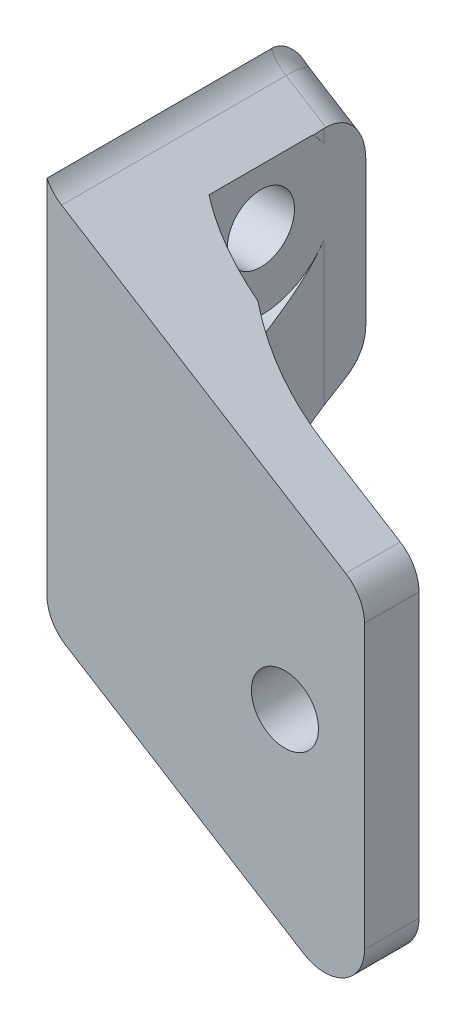
SolidWorks part; units mm, degrees
ref_plane "Front Plane" through (0, 0, 0) normal (0, 0, 1) x (1, 0, 0)
ref_plane "Top Plane" through (0, 0, 0) normal (0, 1, 0) x (1, 0, 0)
ref_plane "Right Plane" through (0, 0, 0) normal (1, 0, 0) x (0, 0, -1)
sketch "Sketch1" plane through (0, 0, 0) normal (0, 0, 1) x (1, 0, 0)
  line L12 (466.0404, -267.15) -> (19.05, 11.077) construction
  line L28 (55.1575, -11.3979) -> (21.2899, 9.6828)
  line L32 (5.7912, 19.05) -> (-5.7912, 19.05)
  line L33 (-19.05, -19.05) -> (-19.05, -52.4)
  line L34 (-14.3, -57.15) -> (52.6474, -57.15)
  line L35 (57.3974, -52.4) -> (57.3974, -15.4305)
  line L36 (-19.05, -13.7235) -> (-19.05, -19.05)
  line L37 (-19.05, -19.05) -> (-19.0952, -18.9748)
  line L38 (-19.05, 5.7912) -> (-19.05, -5.7912)
  line L44 (-19.05, -5.7912) -> (-19.05, -6.9643)
  line L45 (-19.05, -8.9963) -> (-19.05, -13.7235)
  line L46 (-13.7235, -19.05) -> (-8.9963, -19.05)
  line L47 (-6.9643, -19.05) -> (-5.7912, -19.05)
  line L48 (-4.064, -17.3228) -> (-4.064, -16.7132)
  line L49 (-5.7912, -14.986) -> (-8.9963, -14.986)
  line L50 (-9.909, -12.7826) -> (-5.0152, -7.8889)
  line L51 (-2.833, -6.985) -> (2.833, -6.985)
  line L52 (5.0152, -7.8889) -> (9.909, -12.7826)
  line L53 (8.9963, -14.986) -> (5.7912, -14.986)
  line L54 (4.064, -16.7132) -> (4.064, -17.3228)
  line L55 (5.7912, -19.05) -> (6.9643, -19.05)
  line L56 (8.9963, -19.05) -> (13.7235, -19.05)
  line L57 (19.05, -13.7235) -> (19.05, -8.9963)
  line L58 (19.05, -6.9643) -> (19.05, -5.7912)
  line L59 (17.3228, -4.064) -> (16.7132, -4.064)
  line L60 (14.986, -5.7912) -> (14.986, -8.9963)
  line L61 (12.7826, -9.909) -> (7.8889, -5.0152)
  line L62 (6.985, -2.833) -> (6.985, 2.833)
  line L63 (7.8889, 5.0152) -> (12.7826, 9.909)
  line L64 (14.986, 8.9963) -> (14.986, 5.7912)
  line L65 (16.7132, 4.064) -> (17.3228, 4.064)
  line L66 (19.05, 5.7912) -> (19.05, 6.9643)
  line L67 (19.05, 8.9963) -> (19.05, 13.7235)
  line L68 (13.7235, 19.05) -> (8.9963, 19.05)
  line L69 (6.9643, 19.05) -> (5.7912, 19.05)
  line L70 (4.064, 17.3228) -> (4.064, 16.7132)
  line L71 (5.7912, 14.986) -> (8.9963, 14.986)
  line L72 (9.909, 12.7826) -> (5.0152, 7.8889)
  line L73 (2.833, 6.985) -> (-2.833, 6.985)
  line L74 (-5.0152, 7.8889) -> (-9.909, 12.7826)
  line L75 (-8.9963, 14.986) -> (-5.7912, 14.986)
  line L76 (-4.064, 16.7132) -> (-4.064, 17.3228)
  line L77 (-5.7912, 19.05) -> (-6.9643, 19.05)
  line L78 (-8.9963, 19.05) -> (-13.7235, 19.05)
  line L79 (-19.05, 13.7235) -> (-19.05, 8.9963)
  line L80 (-19.05, 6.9643) -> (-19.05, 5.7912)
  line L81 (-17.3228, 4.064) -> (-16.7132, 4.064)
  line L82 (-14.986, 5.7912) -> (-14.986, 8.9963)
  line L83 (-12.7826, 9.909) -> (-7.8889, 5.0152)
  line L84 (-6.985, 2.833) -> (-6.985, -2.833)
  line L85 (-7.8889, -5.0152) -> (-12.7826, -9.909)
  line L86 (-14.986, -8.9963) -> (-14.986, -5.7912)
  line L87 (-16.7132, -4.064) -> (-17.3228, -4.064)
  line L88 (-19.05, -5.7912) -> (-19.05, -6.9643)
  line L89 (-19.05, -8.9963) -> (-19.05, -13.7235)
  line L111 (19.05, 13.7154) -> (19.05, 13.7235)
  line L112 (13.7235, 19.05) -> (8.9963, 19.05)
  line L113 (6.9643, 19.05) -> (5.7912, 19.05)
  line L121 (-5.7912, 19.05) -> (-6.9643, 19.05)
  line L122 (-8.9963, 19.05) -> (-13.7235, 19.05)
  line L123 (-19.05, 13.7235) -> (-19.05, 8.9963)
  line L124 (-19.05, 6.9643) -> (-19.05, 5.7912)
  circle A2 centre (0, 0) radius 4.5
  circle A3 centre (0, -38.1) radius 3.25
  circle A5 centre (47.9138, -29.0681) radius 4
  arc A6 (-19.05, -52.4) -> (-14.3, -57.15) centre (-14.3, -52.4) ccw
  arc A7 (52.6474, -57.15) -> (57.3974, -52.4) centre (52.6474, -52.4) ccw
  arc A8 (57.3974, -15.4305) -> (55.1575, -11.3979) centre (52.6474, -15.4305) ccw
  arc A9 (21.2899, 9.6828) -> (19.05, 13.7154) centre (23.8, 13.7154) cw
  arc A52 (-19.05, -8.9963) -> (-19.05, -6.9643) centre (-19.05, -7.9803) ccw
  arc A53 (-18.8293, -15.7312) -> (-19.05, -13.7235) centre (-19.05, -14.7395) ccw
  arc A54 (-18.8293, -15.7312) -> (-15.7312, -18.8293) centre (-14.3002, -14.3002) ccw
  arc A55 (-13.7235, -19.05) -> (-15.7312, -18.8293) centre (-14.7395, -19.05) ccw
  arc A56 (-6.9643, -19.05) -> (-8.9963, -19.05) centre (-7.9803, -19.05) ccw
  arc A57 (-5.7912, -19.05) -> (-4.064, -17.3228) centre (-5.7912, -17.3228) ccw
  arc A58 (-4.064, -16.7132) -> (-5.7912, -14.986) centre (-5.7912, -16.7132) ccw
  arc A59 (-9.909, -12.7826) -> (-8.9963, -14.986) centre (-8.9963, -13.6953) ccw
  arc A60 (-2.833, -6.985) -> (-5.0152, -7.8889) centre (-2.833, -10.0711) ccw
  arc A61 (5.0152, -7.8889) -> (2.833, -6.985) centre (2.833, -10.0711) ccw
  arc A62 (8.9963, -14.986) -> (9.909, -12.7826) centre (8.9963, -13.6953) ccw
  arc A63 (5.7912, -14.986) -> (4.064, -16.7132) centre (5.7912, -16.7132) ccw
  arc A64 (4.064, -17.3228) -> (5.7912, -19.05) centre (5.7912, -17.3228) ccw
  arc A65 (8.9963, -19.05) -> (6.9643, -19.05) centre (7.9803, -19.05) ccw
  arc A66 (15.7312, -18.8293) -> (13.7235, -19.05) centre (14.7395, -19.05) ccw
  arc A67 (15.7312, -18.8293) -> (18.8293, -15.7312) centre (14.3002, -14.3002) ccw
  arc A68 (19.05, -13.7235) -> (18.8293, -15.7312) centre (19.05, -14.7395) ccw
  arc A69 (19.05, -6.9643) -> (19.05, -8.9963) centre (19.05, -7.9803) ccw
  arc A70 (19.05, -5.7912) -> (17.3228, -4.064) centre (17.3228, -5.7912) ccw
  arc A71 (16.7132, -4.064) -> (14.986, -5.7912) centre (16.7132, -5.7912) ccw
  arc A72 (12.7826, -9.909) -> (14.986, -8.9963) centre (13.6953, -8.9963) ccw
  arc A73 (6.985, -2.833) -> (7.8889, -5.0152) centre (10.0711, -2.833) ccw
  arc A74 (7.8889, 5.0152) -> (6.985, 2.833) centre (10.0711, 2.833) ccw
  arc A75 (14.986, 8.9963) -> (12.7826, 9.909) centre (13.6953, 8.9963) ccw
  arc A76 (14.986, 5.7912) -> (16.7132, 4.064) centre (16.7132, 5.7912) ccw
  arc A77 (17.3228, 4.064) -> (19.05, 5.7912) centre (17.3228, 5.7912) ccw
  arc A78 (19.05, 8.9963) -> (19.05, 6.9643) centre (19.05, 7.9803) ccw
  arc A79 (18.8293, 15.7312) -> (19.05, 13.7235) centre (19.05, 14.7395) ccw
  arc A80 (18.8293, 15.7312) -> (15.7312, 18.8293) centre (14.3002, 14.3002) ccw
  arc A81 (13.7235, 19.05) -> (15.7312, 18.8293) centre (14.7395, 19.05) ccw
  arc A82 (6.9643, 19.05) -> (8.9963, 19.05) centre (7.9803, 19.05) ccw
  arc A83 (5.7912, 19.05) -> (4.064, 17.3228) centre (5.7912, 17.3228) ccw
  arc A84 (4.064, 16.7132) -> (5.7912, 14.986) centre (5.7912, 16.7132) ccw
  arc A85 (9.909, 12.7826) -> (8.9963, 14.986) centre (8.9963, 13.6953) ccw
  arc A86 (2.833, 6.985) -> (5.0152, 7.8889) centre (2.833, 10.0711) ccw
  arc A87 (-5.0152, 7.8889) -> (-2.833, 6.985) centre (-2.833, 10.0711) ccw
  arc A88 (-8.9963, 14.986) -> (-9.909, 12.7826) centre (-8.9963, 13.6953) ccw
  arc A89 (-5.7912, 14.986) -> (-4.064, 16.7132) centre (-5.7912, 16.7132) ccw
  arc A90 (-4.064, 17.3228) -> (-5.7912, 19.05) centre (-5.7912, 17.3228) ccw
  arc A91 (-8.9963, 19.05) -> (-6.9643, 19.05) centre (-7.9803, 19.05) ccw
  arc A92 (-15.7312, 18.8293) -> (-13.7235, 19.05) centre (-14.7395, 19.05) ccw
  arc A93 (-15.7312, 18.8293) -> (-18.8293, 15.7312) centre (-14.3002, 14.3002) ccw
  arc A94 (-19.05, 13.7235) -> (-18.8293, 15.7312) centre (-19.05, 14.7395) ccw
  arc A95 (-19.05, 6.9643) -> (-19.05, 8.9963) centre (-19.05, 7.9803) ccw
  arc A96 (-19.05, 5.7912) -> (-17.3228, 4.064) centre (-17.3228, 5.7912) ccw
  arc A97 (-16.7132, 4.064) -> (-14.986, 5.7912) centre (-16.7132, 5.7912) ccw
  arc A98 (-12.7826, 9.909) -> (-14.986, 8.9963) centre (-13.6953, 8.9963) ccw
  arc A99 (-6.985, 2.833) -> (-7.8889, 5.0152) centre (-10.0711, 2.833) ccw
  arc A100 (-7.8889, -5.0152) -> (-6.985, -2.833) centre (-10.0711, -2.833) ccw
  arc A101 (-14.986, -8.9963) -> (-12.7826, -9.909) centre (-13.6953, -8.9963) ccw
  arc A102 (-14.986, -5.7912) -> (-16.7132, -4.064) centre (-16.7132, -5.7912) ccw
  arc A103 (-17.3228, -4.064) -> (-19.05, -5.7912) centre (-17.3228, -5.7912) ccw
  arc A104 (-19.05, -8.9963) -> (-19.05, -6.9643) centre (-19.05, -7.9803) ccw
  arc A105 (-18.8293, -15.7312) -> (-19.05, -13.7235) centre (-19.05, -14.7395) ccw
  arc A131 (18.8293, 15.7312) -> (19.05, 13.7235) centre (19.05, 14.7395) ccw
  arc A132 (18.8293, 15.7312) -> (15.7312, 18.8293) centre (14.3002, 14.3002) ccw
  arc A133 (13.7235, 19.05) -> (15.7312, 18.8293) centre (14.7395, 19.05) ccw
  arc A134 (6.9643, 19.05) -> (8.9963, 19.05) centre (7.9803, 19.05) ccw
  arc A143 (-8.9963, 19.05) -> (-6.9643, 19.05) centre (-7.9803, 19.05) ccw
  arc A144 (-15.7312, 18.8293) -> (-13.7235, 19.05) centre (-14.7395, 19.05) ccw
  arc A145 (-15.7312, 18.8293) -> (-18.8293, 15.7312) centre (-14.3002, 14.3002) ccw
  arc A146 (-19.05, 13.7235) -> (-18.8293, 15.7312) centre (-19.05, 14.7395) ccw
  arc A147 (-19.05, 6.9643) -> (-19.05, 8.9963) centre (-19.05, 7.9803) ccw
  dimension "D2" = 4.75
  dimension "D1" = 0
extrude "Boss-Extrude1" add sketch "Sketch1" along normal blind 6.5
sketch "Sketch2" plane through (0, 0, 0) normal (0, 0, -1) x (-1, 0, 0)
  line L53 (-19.55, -57.15) -> (14.3, -57.15)
  line L54 (19.05, -52.4) -> (19.05, -8.9963)
  line L55 (19.05, -6.9643) -> (19.05, 6.9643)
  line L56 (19.05, 8.9963) -> (19.05, 13.7235)
  line L57 (13.7235, 19.05) -> (8.9963, 19.05)
  line L58 (6.9643, 19.05) -> (-6.9643, 19.05)
  line L59 (-8.9963, 19.05) -> (-13.7235, 19.05)
  line L61 (-19.55, -14.612) -> (-19.55, 11.5941)
  line L63 (14.3, -57.15) -> (-52.6474, -57.15) construction
  line L64 (-35.024, -43.7437) -> (-1.1564, -22.663)
  line L65 (-35.024, -43.7437) -> (-19.55, -34.112)
  line L66 (14.3, -57.15) -> (-52.6474, -57.15)
  line L67 (-35.024, -43.7437) -> (-55.2813, -56.3528)
  line L134 (19.05, -8.9963) -> (19.05, -52.4)
  line L135 (14.3, -57.15) -> (-19.55, -57.15)
  line L136 (-19.55, -14.612) -> (-19.55, -34.112)
  arc A157 (14.3, -57.15) -> (19.05, -52.4) centre (14.3, -52.4) ccw
  arc A170 (14.3, -57.15) -> (19.05, -52.4) centre (14.3, -52.4) ccw
  arc A171 (19.05, -6.9643) -> (19.05, -8.9963) centre (19.05, -7.9803) ccw
  arc A172 (19.05, 8.9963) -> (19.05, 6.9643) centre (19.05, 7.9803) ccw
  arc A173 (18.8293, 15.7312) -> (19.05, 13.7235) centre (19.05, 14.7395) ccw
  arc A174 (18.8293, 15.7312) -> (15.7312, 18.8293) centre (14.3002, 14.3002) ccw
  arc A175 (13.7235, 19.05) -> (15.7312, 18.8293) centre (14.7395, 19.05) ccw
  arc A176 (6.9643, 19.05) -> (8.9963, 19.05) centre (7.9803, 19.05) ccw
  arc A177 (-8.9963, 19.05) -> (-6.9643, 19.05) centre (-7.9803, 19.05) ccw
  arc A178 (-15.7312, 18.8293) -> (-13.7235, 19.05) centre (-14.7395, 19.05) ccw
  arc A179 (-15.7312, 18.8293) -> (-18.8293, 15.7312) centre (-14.3002, 14.3002) ccw
  arc A180 (-19.05, 13.7235) -> (-18.8293, 15.7312) centre (-19.05, 14.7395) ccw
  arc A181 (-19.55, 11.5941) -> (-19.05, 13.7154) centre (-23.8, 13.7154) ccw
  arc A182 (-57.3974, -52.4) -> (-52.6474, -57.15) centre (-52.6474, -52.4) ccw construction
  arc A183 (-55.2813, -56.3528) -> (-52.6474, -57.15) centre (-52.6474, -52.4) ccw
  line M170 (19.05, -52.4) -> (19.05, -8.9963)
  arc M171 (19.05, -8.9963) -> (19.05, -6.9643) centre (19.05, -7.9803) cw
  line M172 (19.05, -6.9643) -> (19.05, 6.9643)
  arc M173 (19.05, 6.9643) -> (19.05, 8.9963) centre (19.05, 7.9803) cw
  line M174 (19.05, 8.9963) -> (19.05, 13.7235)
  arc M175 (19.05, 13.7235) -> (18.8293, 15.7312) centre (19.05, 14.7395) cw
  arc M176 (18.8293, 15.7312) -> (15.7312, 18.8293) centre (14.3002, 14.3002) ccw
  arc M177 (15.7312, 18.8293) -> (13.7235, 19.05) centre (14.7395, 19.05) cw
  line M178 (13.7235, 19.05) -> (8.9963, 19.05)
  arc M179 (8.9963, 19.05) -> (6.9643, 19.05) centre (7.9803, 19.05) cw
  line M180 (6.9643, 19.05) -> (-6.9643, 19.05)
  arc M181 (-6.9643, 19.05) -> (-8.9963, 19.05) centre (-7.9803, 19.05) cw
  line M182 (-8.9963, 19.05) -> (-13.7235, 19.05)
  arc M183 (-13.7235, 19.05) -> (-15.7312, 18.8293) centre (-14.7395, 19.05) cw
  arc M184 (-15.7312, 18.8293) -> (-18.8293, 15.7312) centre (-14.3002, 14.3002) ccw
  arc M185 (-18.8293, 15.7312) -> (-19.05, 13.7235) centre (-19.05, 14.7395) cw
  line M186 (-19.05, 13.7235) -> (-19.05, 13.7154)
  arc M187 (-19.05, 13.7154) -> (-21.2899, 9.6828) centre (-23.8, 13.7154) cw
  line M192 (-52.6474, -57.15) -> (14.3, -57.15)
  arc M193 (14.3, -57.15) -> (19.05, -52.4) centre (14.3, -52.4) ccw
  circle M196 centre (0, -38.1) radius 3.25
  circle M197 centre (0, 0) radius 4.5
  dimension "D1" = 38.1
extrude "Cut-Extrude3" cut sketch "Sketch2" against normal blind 10 contours L61 L136 M192 M193 M170 M171 M172 M173 M174 M175 M176 M177 M178 M179 M180 M181 M182 M183 M184 M185 M186 M187 M197 M196
sketch "Sketch3" plane through (19.55, 0, 0) normal (-1, 0, 0) x (0, 0, 1)
  line L2 (0, 11.5941) -> (-25, 11.5941)
  line L3 (-25, 11.5941) -> (-25, -18.8293)
  line L6 (0, -34.112) -> (0, 11.5941) construction
  line L7 (0, -34.112) -> (0, 11.5941)
  line L8 (0, -34.112) -> (-25, -18.8293)
  circle A0 centre (-12.5, 0.1707) radius 4
extrude "Boss-Extrude2" add sketch "Sketch3" against normal blind 6.5
fillet "Fillet1" radius 20 1 edges at (26.05, -13.696, 0)
fillet "Fillet2" radius 4.75 2 edges at (19.55, -34.112, 3.25) (55.2813, -56.3528, 3.25)
sketch "Sketch4" plane through (0, 0, 0) normal (0, 0, 1) x (1, 0, 0)
  line L3 (21.2899, 9.6828) -> (26.05, 6.7199)
  line L4 (26.05, 6.7199) -> (26.05, 11.5941)
  line L5 (26.05, 11.5941) -> (19.55, 11.5941)
  line L6 (21.2899, 9.6828) -> (26.05, 6.7199)
  line L7 (26.05, 6.7199) -> (26.05, 11.5941)
  line L8 (26.05, 11.5941) -> (19.55, 11.5941)
  arc A1 (19.55, 11.5941) -> (21.2899, 9.6828) centre (23.8, 13.7154) ccw
  arc A2 (19.55, 11.5941) -> (21.2899, 9.6828) centre (23.8, 13.7154) ccw
  dimension "D1" = 0
extrude "Cut-Extrude4" cut sketch "Sketch4" against normal through all
fillet "Fillet3" radius 4.75 4 edges at (20.2875, 10.5178, -25) (33.2001, -34.112, 0) (22.8, -18.8293, -25) (23.67, 8.2014, -25)
sketch "Sketch5" plane through (26.05, 0, 0) normal (1, 0, 0) x (0, 0, -1)
  circle A2 centre (12.5, 0.1707) radius 9
  circle A3 centre (12.5, 0.1707) radius 9
  dimension "D1" = 5
extrude "Cut-Extrude5" cut sketch "Sketch5" along normal through all
sketch "Sketch6" plane through (0, 0, 0) normal (0, 0, -1) x (-1, 0, 0)
  circle A3 centre (-47.9138, -29.0681) radius 9
  circle A4 centre (-47.9138, -29.0681) radius 9
  dimension "D1" = 5
extrude "Cut-Extrude6" cut sketch "Sketch6" along normal blind 10
